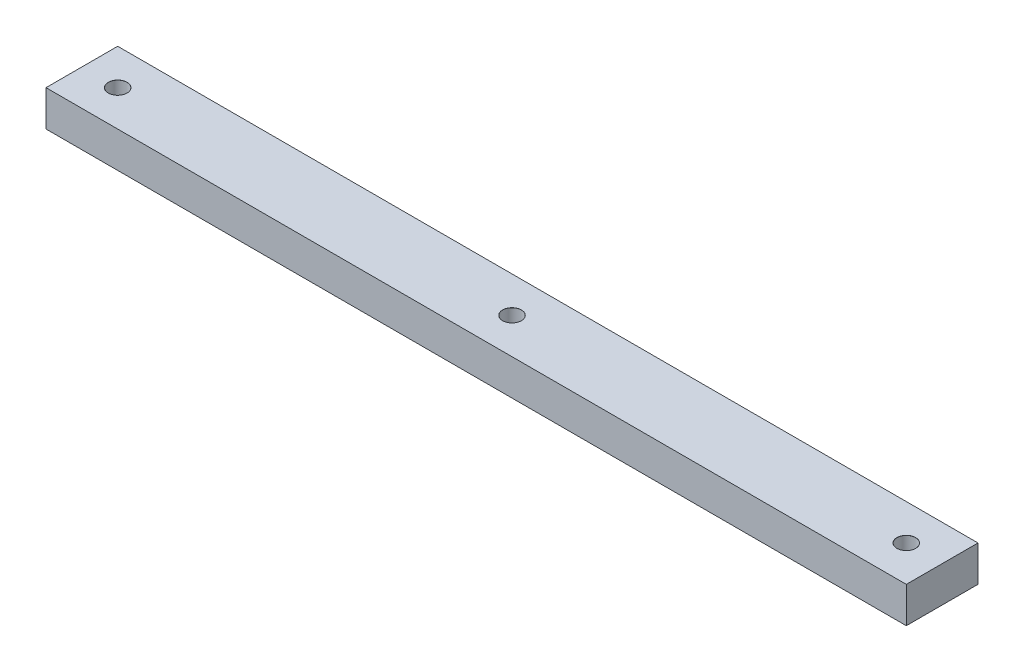
SolidWorks part; units mm, degrees
ref_plane "Front Plane" through (0, 0, 0) normal (0, 0, 1) x (1, 0, 0)
ref_plane "Top Plane" through (0, 0, 0) normal (0, 1, 0) x (1, 0, 0)
ref_plane "Right Plane" through (0, 0, 0) normal (1, 0, 0) x (0, 0, -1)
sketch "Sketch1" plane through (0, 0, 0) normal (0, 1, 0) x (1, 0, 0)
  line L0 (0, 0) -> (0, 37.5156) construction
  line L1 (152.4, -12.7) -> (-152.4, -12.7)
  line L2 (152.4, -12.7) -> (152.4, 12.7)
  line L3 (152.4, 12.7) -> (-152.4, 12.7)
  line L4 (-152.4, -12.7) -> (-152.4, 12.7)
  line L5 (152.4, -12.7) -> (-152.4, 12.7) construction
  line L6 (152.4, 12.7) -> (-152.4, -12.7) construction
  point P0 (0, 0)
  point P6 (-139.7, 0)
  point P8 (-152.4, 0)
  point P10 (139.7, 0)
  dimension "D1" = 304.8
  dimension "D2" = 25.4
  dimension "D3" = 12.7
extrude "Boss-Extrude1" add sketch "Sketch1" along normal blind 12.7
hole_wizard "M6 Clearance Hole1" positions "3DSketch1" profile "Sketch2" hole size "M6" standard "ANSI Metric" end condition through all
sketch3d "3DSketch1"
  point P0 (0, 12.7, 0)
  point P4 (-139.7, 12.7, 0)
  point P6 (139.7, 12.7, 0)
sketch "Sketch2" plane through (0, 12.7, 0) normal (1, 0, 0) x (0, 0, 1)
  line L0 (0, 0) -> (0, 12.7)
  line L1 (0, 12.7) -> (3.3, 12.7)
  line L2 (3.3, 12.7) -> (3.3, 0.025)
  line L3 (3.3, 0.025) -> (3.325, 0)
  line L5 (3.325, 0) -> (0, 0)
  line L6 (-3.3, 0.025) -> (-3.325, 0) construction
  line L11 (0, -6.35) -> (0, 107.95) construction
  dimension "Thru Hole Dia." = 6.6
  dimension "Thru Hole Depth" = 12.7
  dimension "Near C'Sink Dia." = 6.65
  dimension "Near C'Sink Angle" = 90
equation "\"Rover_Length\"= 25in"
equation "\"Rover_Width\"= 18in"
equation "\"Rover_Height\"= 12in"
equation "\"Chassis_Wheelbase\"= 28in"
equation "\"Chassis_WheelDiam\"= 171mm"
equation "\"Chassis_ArmDiamWidth\"= 0.75in"
equation "\"Chassis_ArmAngle\"= 135deg"
equation "\"Chassis_ArmHeight\"= 8in"
equation "\"Chassis_HubMountOD\"= 3in"
equation "\"Chassis_WheelBoltHole\"= 36mm"
equation "\"Chassis_WheelBoltNum\"= 4"
equation "\"Chassis_DiffBarLength\"= 12in"
equation "\"Chassis_DiffBarWidth\"= 1in"
equation "\"Chassis_DiffBarHeight\"= 0.5in"
equation "\"Chassis_DiffLinkage_Length\"= 2.5in"
equation "\"Chassis_MountBracketThickness\"= 0.125in"
equation "\"Chassis_MountBracketWidth\"= 3in"
equation "\"Chassis_MountBacketOverlap\"= 0.5in"
equation "\"Chassis_ArmShaftDiam\"= 0.75in"
equation "\"Chassis_ArmHoleSpacing\" = 1.25in"
equation "\"D1@Sketch1\"=\"Chassis_DiffBarLength\""
equation "\"D2@Sketch1\"=\"Chassis_DiffBarWidth\""
equation "\"D1@Boss-Extrude1\"=\"Chassis_DiffBarHeight\""
